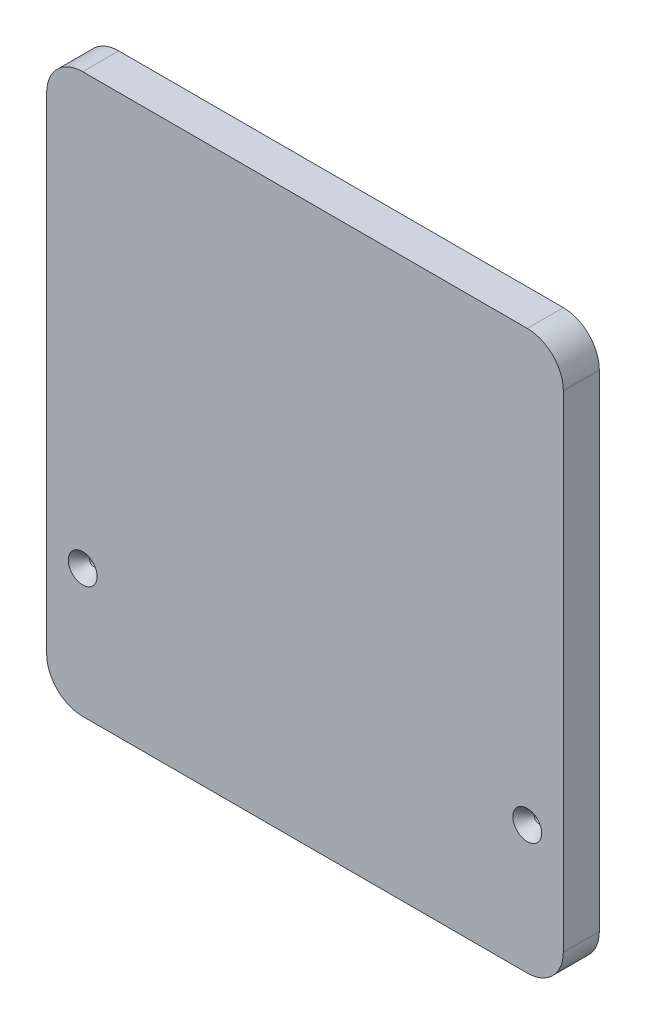
SolidWorks part; units mm, degrees
material "Beech"
ref_plane "Front Plane" through (0, 0, 0) normal (0, 0, 1) x (1, 0, 0)
ref_plane "Top Plane" through (0, 0, 0) normal (0, 1, 0) x (1, 0, 0)
ref_plane "Right Plane" through (0, 0, 0) normal (1, 0, 0) x (0, 0, -1)
sketch "Sketch1" plane through (0, 0, 0) normal (0, 0, 1) x (1, 0, 0)
  line L0 (139.05, 899.8522) -> (139.05, 151.949) construction
  line L1 (-43.1, 899.8522) -> (-43.1, 151.949) construction
  line L2 (-43.1, 906.2022) -> (139.05, 906.2022) construction
  line L8 (139.05, 668.0772) -> (139.05, 864.9272)
  line L9 (139.05, 864.9272) -> (-43.1, 864.9272)
  line L10 (-43.1, 864.9272) -> (-43.1, 668.0772)
  line L11 (-43.1, 668.0772) -> (139.05, 668.0772)
  dimension "D1" = 196.85
  dimension "D2" = 41.275
extrude "Boss-Extrude1" add sketch "Sketch1" along normal blind 12.7
fillet "Fillet1" radius 12.7 4 edges at (139.05, 864.9272, 6.35) (139.05, 668.0772, 6.35) (-43.1, 668.0772, 6.35) (-43.1, 864.9272, 6.35)
hole_wizard "Hole1" positions "Sketch2" profile "Sketch3" legacy
sketch "Sketch2" plane through (47.975, -425.4348, 12.7) normal (0, 0, 1) x (1, 0, 0)
  point P0 (-78.375, 1310.1878)
  point P3 (-78.375, 1138.7378)
  point P6 (78.375, 1138.7378)
  point P9 (78.375, 1310.1878)
sketch "Sketch3" plane through (-30.4, 884.753, 12.7) normal (1, 0, 0) x (0, -1, 0)
  line L0 (0, 0) -> (0, 32.7039)
  line L1 (0, 32.7039) -> (1.5875, 31.75)
  line L2 (1.5875, 31.75) -> (1.5875, 4.0177)
  line L3 (1.5875, 4.0177) -> (5.08, 0)
  line L4 (5.08, 0) -> (0, 0)
  line L5 (0, -14.3089) -> (0, 102.4216) construction
  line L6 (0, 32.7039) -> (-1.5875, 31.75) construction
  line L7 (-1.5875, 4.0177) -> (-5.08, 0) construction
  dimension "Diameter" = 3.175
  dimension "Depth" = 31.75
  dimension "C-Sink Diameter" = 10.16
  dimension "C-Sink Angle" = 82
  dimension "Drill Angle" = 118
